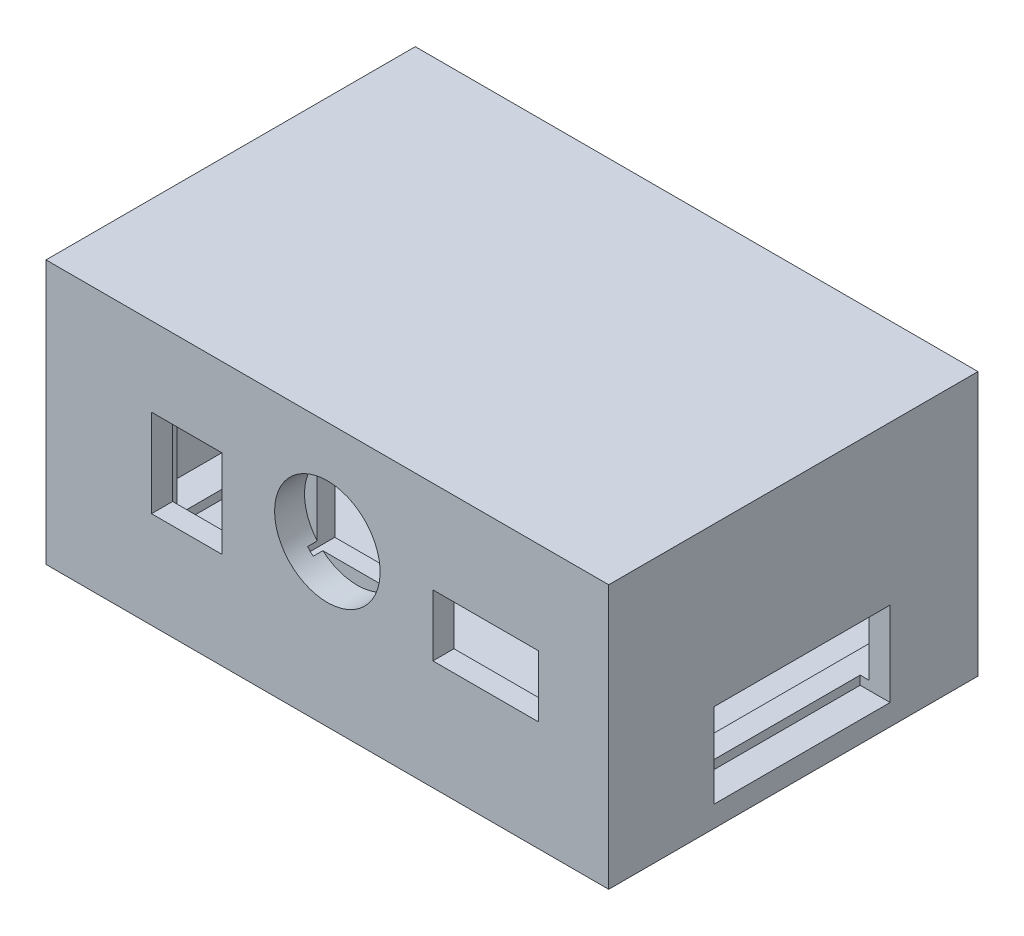
SolidWorks part; units mm, degrees
ref_plane "Front Plane" through (0, 0, 0) normal (0, 0, 1) x (1, 0, 0)
ref_plane "Top Plane" through (0, 0, 0) normal (0, 1, 0) x (1, 0, 0)
ref_plane "Right Plane" through (0, 0, 0) normal (1, 0, 0) x (0, 0, -1)
sketch "Sketch1" plane through (0, 0, 0) normal (0, 0, 1) x (1, 0, 0)
  line L1 (-32, 50) -> (32, 50)
  line L2 (-32, 50) -> (-32, 80)
  line L3 (-32, 80) -> (32, 80)
  line L4 (32, 50) -> (32, 80)
extrude "Boss-Extrude1" add sketch "Sketch1" along normal blind 42 from offset 80
sketch "Sketch2" plane through (0, 0, 0) normal (0, 0, 1) x (1, 0, 0)
  line L1 (-29.6, 52.4) -> (29.6, 52.4)
  line L2 (-29.6, 52.4) -> (-29.6, 77.6)
  line L3 (-29.6, 77.6) -> (29.6, 77.6)
  line L4 (29.6, 52.4) -> (29.6, 77.6)
extrude "Boss-Extrude2" add sketch "Sketch2" along normal blind 40.6 from offset 79 separate body
combine bodies "Combine1" operation type subtract main body 101 bodies to subtract 102
sketch "Sketch3" plane through (0, 0, 0) normal (0, 0, 1) x (1, 0, 0)
  line L1 (-32, 50) -> (32, 50)
  line L2 (-32, 50) -> (-32, 60)
  line L3 (-32, 60) -> (32, 60)
  line L4 (32, 50) -> (32, 60)
extrude "Boss-Extrude3" add sketch "Sketch3" along normal blind 2.4 from offset 80
sketch "Sketch4" plane through (0, 0, 0) normal (0, 0, 1) x (1, 0, 0)
  line L1 (-31, 61.2) -> (-23.2, 61.2)
  line L2 (-31, 61.2) -> (-31, 72.8)
  line L3 (-31, 72.8) -> (-23.2, 72.8)
  line L4 (-23.2, 61.2) -> (-23.2, 72.8)
extrude "Boss-Extrude4" add sketch "Sketch4" along normal blind 6 from offset 80
sketch "Sketch5" plane through (0, 0, 0) normal (0, 0, 1) x (1, 0, 0)
  circle A0 centre (-26, 64) radius 1
extrude "Boss-Extrude5" add sketch "Sketch5" along normal blind 8 from offset 79 separate body
combine bodies "Combine2" operation type subtract main body 105 bodies to subtract 106
sketch "Sketch6" plane through (0, 0, 0) normal (0, 0, 1) x (1, 0, 0)
  circle A0 centre (-26, 70) radius 1
extrude "Boss-Extrude6" add sketch "Sketch6" along normal blind 8 from offset 79 separate body
combine bodies "Combine3" operation type subtract main body 107 bodies to subtract 108
sketch "Sketch7" plane through (0, 0, 0) normal (0, 0, 1) x (1, 0, 0)
  line L1 (23.2, 61.2) -> (31, 61.2)
  line L2 (23.2, 61.2) -> (23.2, 72.8)
  line L3 (23.2, 72.8) -> (31, 72.8)
  line L4 (31, 61.2) -> (31, 72.8)
extrude "Boss-Extrude7" add sketch "Sketch7" along normal blind 6 from offset 80
sketch "Sketch8" plane through (0, 0, 0) normal (0, 0, 1) x (1, 0, 0)
  circle A0 centre (26, 64) radius 1
extrude "Boss-Extrude8" add sketch "Sketch8" along normal blind 8 from offset 79 separate body
combine bodies "Combine4" operation type subtract main body 110 bodies to subtract 111
sketch "Sketch9" plane through (0, 0, 0) normal (0, 0, 1) x (1, 0, 0)
  circle A0 centre (26, 70) radius 1
extrude "Boss-Extrude9" add sketch "Sketch9" along normal blind 8 from offset 79 separate body
combine bodies "Combine5" operation type subtract main body 112 bodies to subtract 113
sketch "Sketch10" plane through (0, 0, 0) normal (0, 0, 1) x (1, 0, 0)
  line L1 (-29.6, 52.4) -> (-26, 52.4)
  line L2 (-29.6, 52.4) -> (-29.6, 53.4)
  line L3 (-29.6, 53.4) -> (-26, 53.4)
  line L4 (-26, 52.4) -> (-26, 53.4)
extrude "Boss-Extrude10" add sketch "Sketch10" along normal blind 28 from offset 86
sketch "Sketch11" plane through (0, 0, 0) normal (0, 0, 1) x (1, 0, 0)
  line L1 (26, 52.4) -> (29.6, 52.4)
  line L2 (26, 52.4) -> (26, 53.4)
  line L3 (26, 53.4) -> (29.6, 53.4)
  line L4 (29.6, 52.4) -> (29.6, 53.4)
extrude "Boss-Extrude11" add sketch "Sketch11" along normal blind 28 from offset 86
sketch "Sketch12" plane through (0, 0, 0) normal (0, 0, 1) x (1, 0, 0)
  line L1 (28.6, 52.4) -> (33, 52.4)
  line L2 (28.6, 52.4) -> (28.6, 62)
  line L3 (28.6, 62) -> (33, 62)
  line L4 (33, 52.4) -> (33, 62)
extrude "Boss-Extrude12" add sketch "Sketch12" along normal blind 20 from offset 90 separate body
combine bodies "Combine6" operation type subtract main body 116 bodies to subtract 117
sketch "Sketch13" plane through (0, 0, 0) normal (0, 0, 1) x (1, 0, 0)
  line L1 (-6.5, 61.75) -> (6.5, 61.75)
  line L2 (-6.5, 61.75) -> (-6.5, 74.75)
  line L3 (-6.5, 74.75) -> (6.5, 74.75)
  line L4 (6.5, 61.75) -> (6.5, 74.75)
extrude "Boss-Extrude13" add sketch "Sketch13" along normal blind 3 from offset 116.6
sketch "Sketch14" plane through (0, 0, 0) normal (0, 0, 1) x (1, 0, 0)
  line L1 (-4.55, 63.7) -> (4.55, 63.7)
  line L2 (-4.55, 63.7) -> (-4.55, 72.8)
  line L3 (-4.55, 72.8) -> (4.55, 72.8)
  line L4 (4.55, 63.7) -> (4.55, 72.8)
extrude "Boss-Extrude14" add sketch "Sketch14" along normal blind 4.1 from offset 115.6 separate body
combine bodies "Combine7" operation type subtract main body 119 bodies to subtract 120
sketch "Sketch15" plane through (0, 0, 0) normal (0, 0, 1) x (1, 0, 0)
  circle A0 centre (0, 68.25) radius 6
extrude "Boss-Extrude15" add sketch "Sketch15" along normal blind 4.4 from offset 118.6 separate body
combine bodies "Combine8" operation type subtract main body 121 bodies to subtract 122
sketch "Sketch16" plane through (0, 0, 0) normal (0, 0, 1) x (1, 0, 0)
  line L1 (7.4, 57.8) -> (8, 57.8)
  line L2 (7.4, 57.8) -> (7.4, 74.2)
  line L3 (7.4, 74.2) -> (8, 74.2)
  line L4 (8, 57.8) -> (8, 74.2)
extrude "Boss-Extrude16" add sketch "Sketch16" along normal blind 2.5 from offset 117.1
sketch "Sketch17" plane through (0, 0, 0) normal (0, 0, 1) x (1, 0, 0)
  line L1 (28.5, 57.8) -> (29.6, 57.8)
  line L2 (28.5, 57.8) -> (28.5, 74.2)
  line L3 (28.5, 74.2) -> (29.6, 74.2)
  line L4 (29.6, 57.8) -> (29.6, 74.2)
extrude "Boss-Extrude17" add sketch "Sketch17" along normal blind 2.5 from offset 117.1
sketch "Sketch18" plane through (0, 0, 0) normal (0, 0, 1) x (1, 0, 0)
  line L1 (12, 62.5) -> (24, 62.5)
  line L2 (12, 62.5) -> (12, 69.5)
  line L3 (12, 69.5) -> (24, 69.5)
  line L4 (24, 62.5) -> (24, 69.5)
extrude "Boss-Extrude18" add sketch "Sketch18" along normal blind 4.4 from offset 118.6 separate body
combine bodies "Combine9" operation type subtract main body 125 bodies to subtract 126
sketch "Sketch19" plane through (0, 0, 0) normal (0, 0, 1) x (1, 0, 0)
  line L1 (-23.2, 52.4) -> (-22, 52.4)
  line L2 (-23.2, 52.4) -> (-23.2, 77.6)
  line L3 (-23.2, 77.6) -> (-22, 77.6)
  line L4 (-22, 52.4) -> (-22, 77.6)
extrude "Boss-Extrude19" add sketch "Sketch19" along normal blind 2.5 from offset 117.1
sketch "Sketch20" plane through (0, 0, 0) normal (0, 0, 1) x (1, 0, 0)
  line L1 (-10, 52.4) -> (-8.8, 52.4)
  line L2 (-10, 52.4) -> (-10, 77.6)
  line L3 (-10, 77.6) -> (-8.8, 77.6)
  line L4 (-8.8, 52.4) -> (-8.8, 77.6)
extrude "Boss-Extrude20" add sketch "Sketch20" along normal blind 2.5 from offset 117.1
sketch "Sketch21" plane through (0, 0, 0) normal (0, 0, 1) x (1, 0, 0)
  line L1 (-20, 61) -> (-12, 61)
  line L2 (-20, 61) -> (-20, 71)
  line L3 (-20, 71) -> (-12, 71)
  line L4 (-12, 61) -> (-12, 71)
extrude "Boss-Extrude21" add sketch "Sketch21" along normal blind 4.4 from offset 118.6 separate body
combine bodies "Combine10" operation type subtract main body 129 bodies to subtract 130
